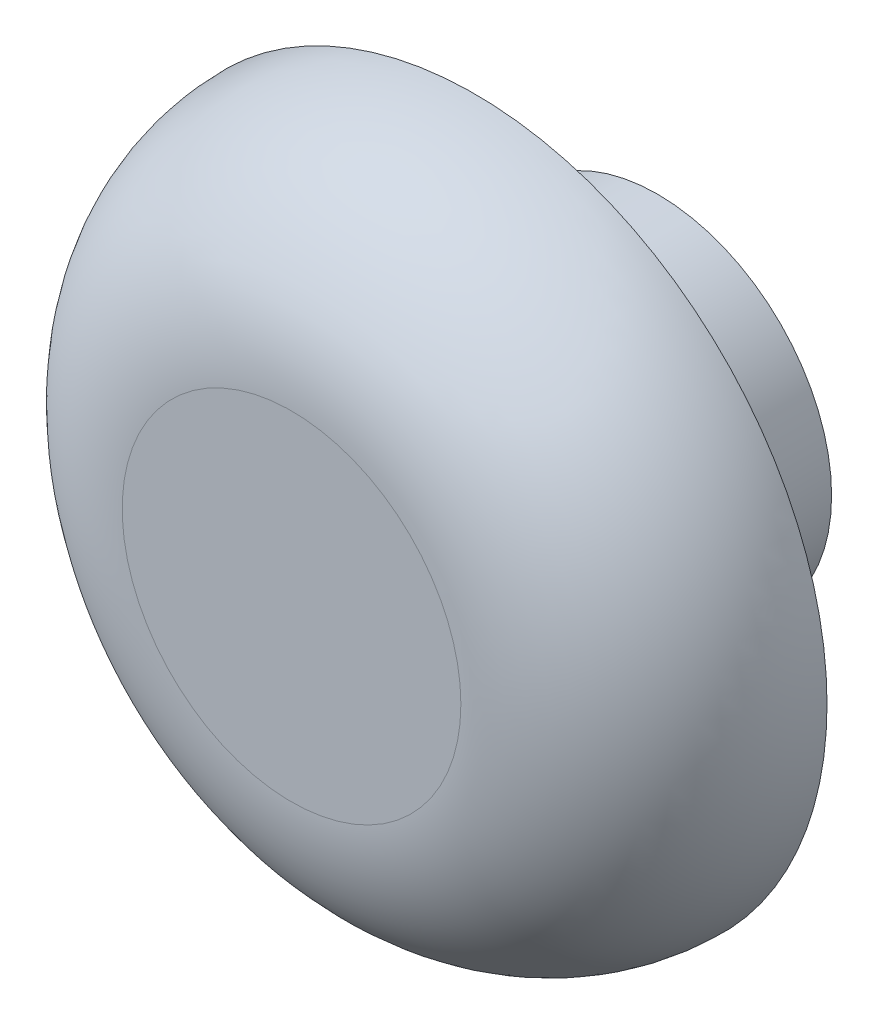
SolidWorks part; units mm, degrees
ref_plane "Płaszczyzna przednia" through (0, 0, 0) normal (0, 0, 1) x (1, 0, 0)
ref_plane "Płaszczyzna górna" through (0, 0, 0) normal (0, 1, 0) x (1, 0, 0)
ref_plane "Płaszczyzna prawa" through (0, 0, 0) normal (1, 0, 0) x (0, 0, -1)
sketch "Szkic1" plane through (0, 0, 0) normal (0, 0, 1) x (1, 0, 0)
  circle A0 centre (0, 0) radius 1.9
  dimension "D1" = 3.8
extrude "Dodanie-wyciągnięcie1" add sketch "Szkic1" along normal blind 2
sketch "Szkic3" plane through (0, 0, 2) normal (0, 0, 1) x (1, 0, 0)
  circle A0 centre (0, 0) radius 3.85
  dimension "D1" = 7.7
extrude "Dodanie-wyciągnięcie2" add sketch "Szkic3" along normal blind 2
fillet "Zaokrąglenie1" radius 2 1 edges at (3.85, 0, 4)
